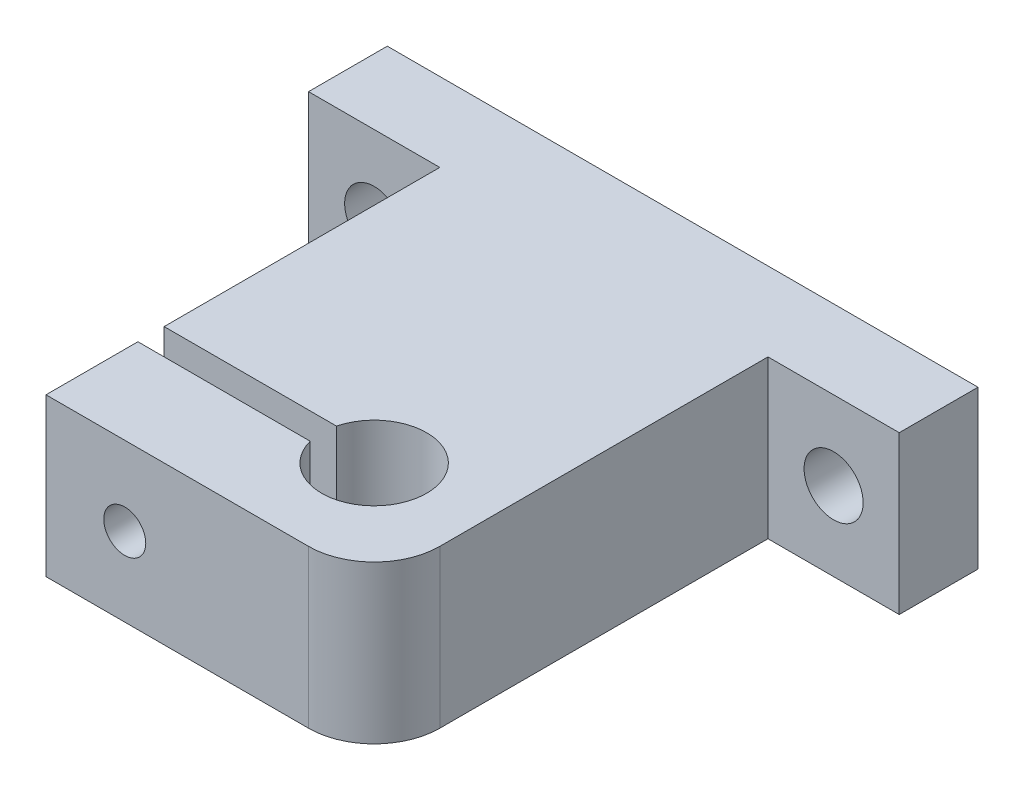
SolidWorks part; units mm, degrees
material "Copper"
ref_plane "Front Plane" through (0, 0, 0) normal (0, 0, 1) x (1, 0, 0)
ref_plane "Top Plane" through (0, 0, 0) normal (0, 1, 0) x (1, 0, 0)
ref_plane "Right Plane" through (0, 0, 0) normal (1, 0, 0) x (0, 0, -1)
sketch "Sketch2" plane through (0, 0, 0) normal (0, 0, 1) x (1, 0, 0)
  line L1 (0, 0) -> (45, 0)
  line L2 (0, 0) -> (0, 12)
  line L3 (0, 12) -> (45, 12)
  line L4 (45, 0) -> (45, 12)
  circle A0 centre (5, 6) radius 2.25
  circle A1 centre (40, 6) radius 2.25
  dimension "D1" = 5
  dimension "D2" = 6
  dimension "D3" = 5
  dimension "D4" = 6
extrude "Boss-Extrude1" add sketch "Sketch2" along normal blind 6
sketch "Sketch3" plane through (0, 0, 6) normal (0, 0, 1) x (1, 0, 0)
  line L0 (0, 0) -> (45, 0) construction
  line L1 (10, 0) -> (35, 0)
  line L2 (10, 0) -> (10, 12)
  line L3 (10, 12) -> (35, 12)
  line L4 (35, 0) -> (35, 12)
  line L5 (45, 12) -> (0, 12) construction
  line L6 (0, 12) -> (0, 0) construction
  line L7 (45, 0) -> (45, 12) construction
  dimension "D1" = 25
  dimension "D2" = 10
  dimension "D3" = 10
extrude "Boss-Extrude2" add sketch "Sketch3" along normal blind 30
fillet "Fillet1" radius 5 1 edges at (35, 6, 36)
sketch "Sketch4" plane through (0, 0, 0) normal (0, -1, 0) x (1, 0, 0)
  line L0 (10, 36) -> (30, 36) construction
  line L1 (35, 31) -> (35, 6) construction
  line L2 (0, 0) -> (45, 0) construction
  line L3 (23.127, 29) -> (10, 29)
  line L4 (10, 36) -> (10, 6) construction
  line L5 (10, 29) -> (10, 27)
  line L6 (10, 27) -> (23.127, 27)
  circle A0 centre (27, 28) radius 4
  line M4 (10, 36) -> (10, 6)
  dimension "D1" = 8
  dimension "D5" = 8
  dimension "D2" = 8
  dimension "D3" = 28
  dimension "D4" = 1
  dimension "D6" = 1
extrude "Cut-Extrude2" cut sketch "Sketch4" against normal blind 30 contours A0 L3 L6 M4 | A0 region at (16.5211, 0, 28) region at (27, 0, 28)
sketch "Sketch5" plane through (0, 0, 0) normal (0, 0, -1) x (-1, 0, 0)
  line L0 (-45, 12) -> (0, 12) construction
  line L1 (-32.6724, 9.5) -> (-12.1585, 9.5)
  line L2 (-32.6724, 9.5) -> (-32.6724, 2.5)
  line L3 (-32.6724, 2.5) -> (-12.1585, 2.5)
  line L4 (-12.1585, 9.5) -> (-12.1585, 2.5)
  line L5 (0, 0) -> (-45, 0) construction
  dimension "D1" = 20.5139
  dimension "D2" = 2.5
  dimension "D3" = 2.5
extrude "Cut-Extrude3" cut sketch "Sketch5" against normal blind 20
sketch "Sketch6" plane through (0, 0, 36) normal (0, 0, 1) x (1, 0, 0)
  line L0 (10, 12) -> (10, 0) construction
  line L1 (30, 12) -> (10, 12) construction
  line L2 (10, 0) -> (30, 0) construction
  circle A0 centre (16, 6) radius 1.6
  dimension "D1" = 6
  dimension "D2" = 6
  dimension "D3" = 6
extrude "Cut-Extrude4" cut sketch "Sketch6" against normal blind 20
sketch "Sketch7" plane through (0, 0, 20) normal (0, 0, -1) x (-1, 0, 0)
  line L1 (-14.4137, 3.2492) -> (-12.8246, 5.9984)
  line L2 (-12.8246, 5.9984) -> (-14.4109, 8.7492)
  line L3 (-14.4109, 8.7492) -> (-17.5863, 8.7508)
  line L4 (-17.5863, 8.7508) -> (-19.1754, 6.0016)
  line L5 (-19.1754, 6.0016) -> (-17.5891, 3.2508)
  line L6 (-17.5891, 3.2508) -> (-14.4137, 3.2492)
  circle A0 centre (-16, 6) radius 2.75 construction
extrude "Cut-Extrude5" cut sketch "Sketch7" against normal blind 3
